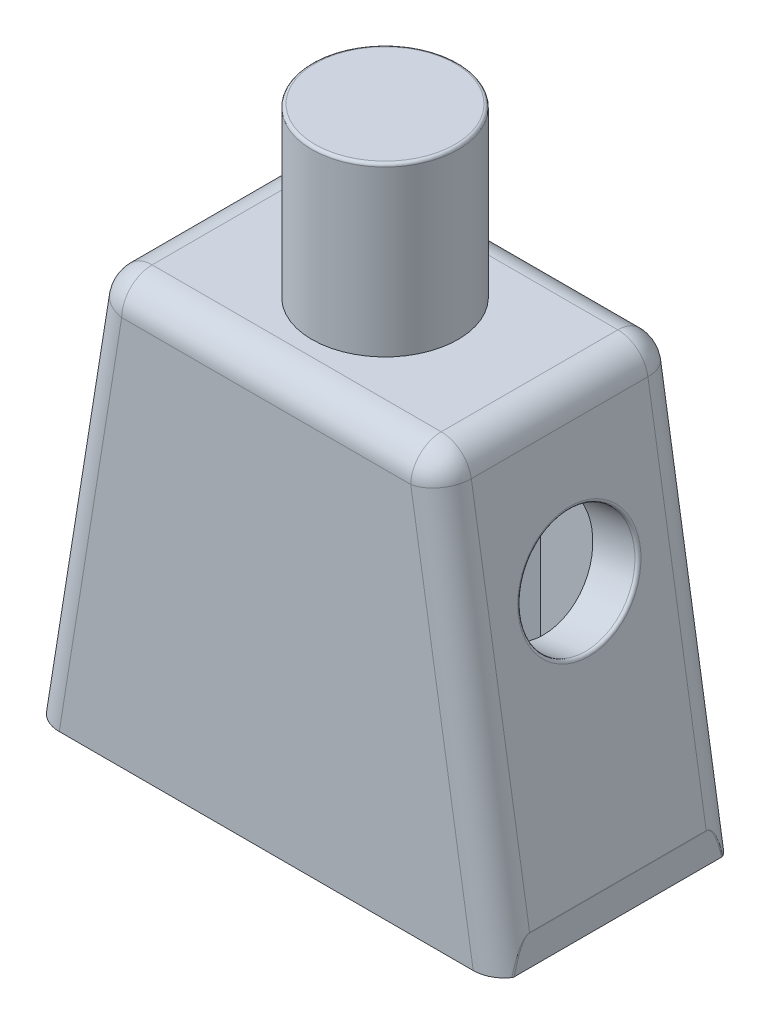
SolidWorks part; units mm, degrees
ref_plane "Front Plane" through (0, 0, 0) normal (0, 0, 1) x (1, 0, 0)
ref_plane "Top Plane" through (0, 0, 0) normal (0, 1, 0) x (1, 0, 0)
ref_plane "Right Plane" through (0, 0, 0) normal (1, 0, 0) x (0, 0, -1)
sketch "Sketch1" plane through (0, 0, 0) normal (0, 0, 1) x (1, 0, 0)
  line L0 (0, 0) -> (0, 13.8) construction
  line L1 (7.65, 0) -> (-7.65, 0)
  line L2 (-7.65, 0) -> (-7.65, 1)
  line L3 (-7.65, 1) -> (-5.6, 13.8)
  line L4 (-5.6, 13.8) -> (5.6, 13.8)
  line L5 (7.65, 1) -> (5.6, 13.8)
  line L6 (7.65, 0) -> (7.65, 1)
  point P5 (0, 0)
  point P8 (0, 0)
  dimension "D1" = 13.8
  dimension "D2" = 1
  dimension "D3" = 15.3
  dimension "D4" = 5.6
extrude "Torso" add sketch "Sketch1" along normal mid plane 7.8
shell "Shell1" thickness 1.5 removed face at (0, 0, 0)
sketch "Sketch2" plane through (-7.6148, 1.2196, 0) normal (-0.9874, 0.1581, 0) x (0, 0, 1)
  line L0 (0, 12.7408) -> (0, -0.2224) construction
  line L1 (3.9, 12.7408) -> (-3.9, 12.7408) construction
  line L2 (3.9, -0.2224) -> (-3.9, -0.2224) construction
  line L3 (3.9, -1.2098) -> (-3.9, -1.2098) construction
  circle A0 centre (0, 7.7902) radius 1.9
  dimension "D1" = 3.8
  dimension "D2" = 9
extrude "Arm Hole" cut sketch "Sketch2" against normal up to next
mirror "Mirror1" about plane through (0, 0, 0) normal (1, 0, 0) of "Arm Hole"
sketch "Sketch3" plane through (0, 0, 0) normal (0, -1, 0) x (1, 0, 0)
  line L0 (0, 3.9) -> (0, 0) construction
  line L1 (-7.65, 3.9) -> (7.65, 3.9) construction
  line L2 (-1.5, 2.4) -> (-1.5, 1.6)
  line L3 (4.3211, 2.4) -> (-4.3211, 2.4) construction
  line L4 (-1.5, 1.6) -> (-2.7, 2.4)
  line L5 (-2.7, 2.4) -> (-1.5, 2.4)
  line L6 (2.7, 2.4) -> (1.5, 2.4)
  line L7 (1.5, 1.6) -> (2.7, 2.4)
  line L8 (1.5, 2.4) -> (1.5, 1.6)
  dimension "D1" = 1.2
  dimension "D2" = 3
  dimension "D3" = 0.8
extrude "Boss-Extrude2" add sketch "Sketch3" against normal up to next
mirror "Mirror2" about plane through (0, 0, 0) normal (0, 0, 1) of "Boss-Extrude2"
sketch "Sketch4" plane through (0, 13.8, 0) normal (0, 1, 0) x (1, 0, 0)
  circle A0 centre (0, 0) radius 2.4
  dimension "D1" = 4.8
extrude "Boss-Extrude3" add sketch "Sketch4" along normal blind 5.5
sketch "Sketch5" plane through (0, 12.3, 0) normal (0, -1, 0) x (1, 0, 0)
  circle A0 centre (0, 0) radius 1.25
  dimension "D1" = 2.5
extrude "Cut-Extrude2" cut sketch "Sketch5" against normal blind 4.25
fillet "Fillet1" radius 1 4 edges at (-6.625, 7.4, 3.9) (-6.625, 7.4, -3.9) (6.625, 7.4, -3.9) (6.625, 7.4, 3.9)
fillet "Fillet3" radius 1 8 edges at (-5.3034, 13.8, -3.6071) (-5.3034, 13.8, 3.6071) (-5.6, 13.8, 0) (0, 13.8, -3.9) (5.3034, 13.8, -3.6071) (5.6, 13.8, 0) (5.3034, 13.8, 3.6071) (0, 13.8, 3.9)
fillet "Fillet4" radius 0.1 9 edges at (-7.65, 0.7449, 3.1812) (-7.65, 0.7449, -3.1812) (7.65, 0.7449, 3.1812) (7.65, 0.7449, -3.1812) (-7.65, 1, 0) (7.65, 1, 0) (6.6834, 7.0357, 0) (-6.6834, 7.0357, 0) (0, 19.3, 2.4)
